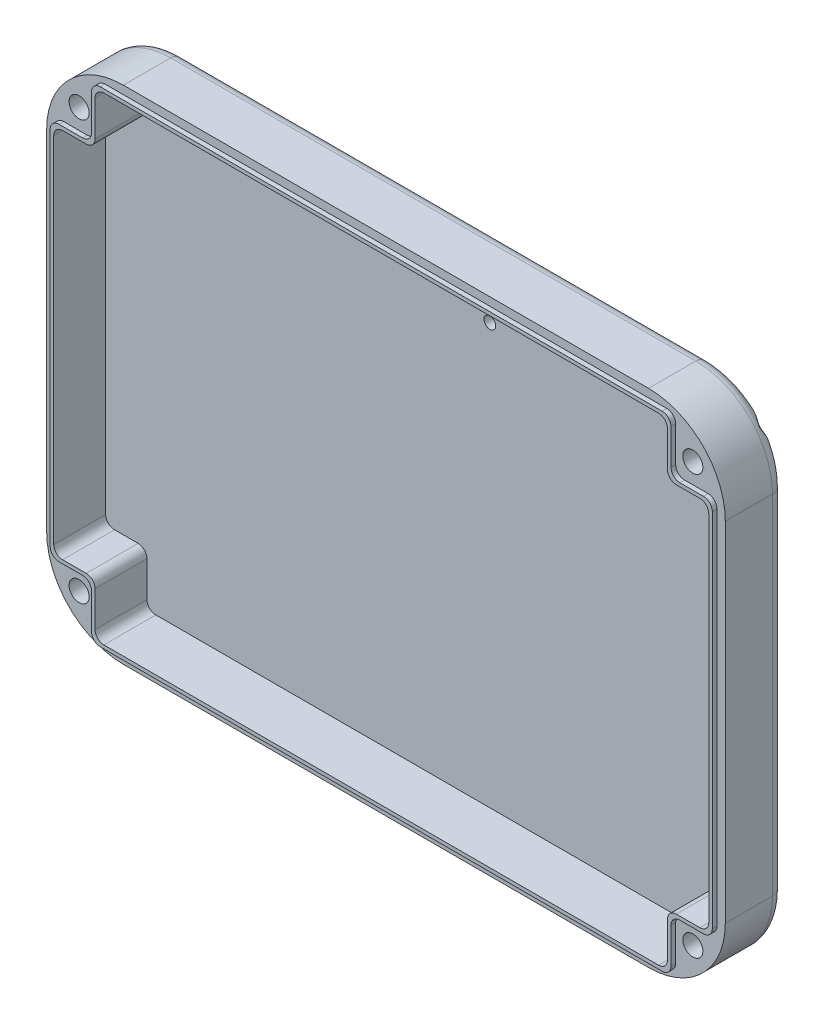
SolidWorks part; units mm, degrees
ref_plane "Спереди" through (0, 0, 0) normal (0, 0, 1) x (1, 0, 0)
ref_plane "Сверху" through (0, 0, 0) normal (0, 1, 0) x (1, 0, 0)
ref_plane "Справа" through (0, 0, 0) normal (1, 0, 0) x (0, 0, -1)
sketch "Sketch1" plane through (0, 0, 0) normal (0, 0, 1) x (1, 0, 0)
  line L1 (-57.5, 85) -> (57.5, 85) construction
  line L2 (-57.5, 85) -> (-57.5, 0) construction
  line L3 (-57.5, 0) -> (57.5, 0) construction
  line L5 (-57.5, 42.5) -> (22.5, 42.5) construction
  line L7 (0, 0) -> (0, 85) construction
  line L10 (-57.5, 85) -> (-57.5, 0) construction
  line L11 (-57.5, 85) -> (57.5, 85)
  line L12 (57.5, 85) -> (57.5, 0) construction
  line L13 (57.5, 0) -> (-57.5, 0)
  line L20 (57.5, 0) -> (57.5, 19)
  line L21 (57.5, 19) -> (57.5, 85)
  line L22 (-57.5, 0) -> (-57.5, 19)
  line L23 (-57.5, 19) -> (-57.5, 85)
  dimension "D1" = 115
  dimension "D2" = 85
extrude "Boss-Extrude1" add sketch "Sketch1" along normal blind 10
shell "Shell1" thickness 2 removed face at (0, 42.5, 10)
sketch "Sketch3" plane through (0, 0, 2) normal (0, 0, 1) x (1, 0, 0)
  line L0 (0, 0) -> (0, 85) construction
  line L1 (55.5, 2) -> (48.5, 2)
  line L2 (55.5, 2) -> (55.5, 11)
  line L3 (55.5, 11) -> (48.5, 11)
  line L4 (48.5, 2) -> (48.5, 11)
  line L5 (-57.5, 0) -> (57.5, 0) construction
  line L6 (57.5, 85) -> (-57.5, 85) construction
  line L7 (-48.5, 2) -> (-48.5, 11)
  line L8 (55.5, 2) -> (55.5, 83) construction
  line L9 (55.5, 42.5) -> (-55.5, 42.5) construction
  line L10 (-55.5, 83) -> (-55.5, 2) construction
  line L11 (-55.5, 11) -> (-48.5, 11)
  line L12 (-55.5, 2) -> (-55.5, 11)
  line L13 (-55.5, 2) -> (-48.5, 2)
  line L14 (-55.5, 83) -> (-48.5, 83)
  line L15 (-55.5, 83) -> (-55.5, 74)
  line L16 (-55.5, 74) -> (-48.5, 74)
  line L17 (-48.5, 83) -> (-48.5, 74)
  line L18 (48.5, 83) -> (48.5, 74)
  line L19 (55.5, 74) -> (48.5, 74)
  line L20 (55.5, 83) -> (55.5, 74)
  line L21 (55.5, 83) -> (48.5, 83)
  line L22 (57.5, 0) -> (57.5, 85) construction
  circle A0 centre (52, 7) radius 1.7
  circle A1 centre (-52, 7) radius 1.7
  circle A2 centre (-52, 78) radius 1.7
  circle A3 centre (52, 78) radius 1.7
  dimension "D3" = 3.4
  dimension "D1" = 7
  dimension "D2" = 9
  dimension "D4" = 7
  dimension "D5" = 5.5
extrude "Boss-Extrude3" add sketch "Sketch3" along normal up to surface (8 mm away) up to face at (0, 42.5, 10)
sketch "Sketch5" plane through (0, 0, 10) normal (0, 0, 1) x (1, 0, 0)
  line L0 (0, 0) -> (0, 85) construction
  line L1 (-57.5, 0) -> (57.5, 0) construction
  line L2 (57.5, 85) -> (-57.5, 85) construction
  line L4 (55.5, 11) -> (55.5, 74) construction
  line L5 (55.5, 42.5) -> (-55.5, 42.5) construction
  line L6 (55.5, 11) -> (55.5, 74) construction
  line L7 (56.1, 10.4) -> (56.1, 54.9886) construction
  line L8 (55.5, 11) -> (48.5, 11)
  line L9 (48.5, 11) -> (48.5, 2)
  line L10 (48.5, 2) -> (0, 2)
  line L11 (-48.5, 2) -> (48.5, 2) construction
  line L42 (55.5, 11) -> (55.5, 42.5)
  line L49 (56.1, 10.4) -> (49.1, 10.4)
  line L50 (49.1, 10.4) -> (49.1, 1.4)
  line L51 (49.1, 1.4) -> (0, 1.4)
  line L52 (-49.1, 1.4) -> (0, 1.4)
  line L53 (-49.1, 10.4) -> (-49.1, 1.4)
  line L54 (-56.1, 10.4) -> (-49.1, 10.4)
  line L58 (-55.5, 11) -> (-55.5, 42.5)
  line L61 (-48.5, 2) -> (0, 2)
  line L62 (-48.5, 11) -> (-48.5, 2)
  line L63 (-55.5, 11) -> (-48.5, 11)
  line L64 (-55.5, 74) -> (-48.5, 74)
  line L65 (-48.5, 74) -> (-48.5, 83)
  line L66 (-48.5, 83) -> (0, 83)
  line L68 (-55.5, 74) -> (-55.5, 42.5)
  line L70 (-56.1, 74.6) -> (-56.1, 10.4)
  line L71 (-56.1, 74.6) -> (-49.1, 74.6)
  line L72 (-49.1, 74.6) -> (-49.1, 83.6)
  line L73 (-49.1, 83.6) -> (0, 83.6)
  line L74 (49.1, 83.6) -> (0, 83.6)
  line L75 (49.1, 74.6) -> (49.1, 83.6)
  line L76 (56.1, 74.6) -> (49.1, 74.6)
  line L77 (56.1, 74.6) -> (56.1, 10.4)
  line L80 (55.5, 74) -> (55.5, 42.5)
  line L83 (48.5, 83) -> (0, 83)
  line L84 (48.5, 74) -> (48.5, 83)
  line L85 (55.5, 74) -> (48.5, 74)
  line L86 (42.6, -85.1835) -> (42.6, 29) construction
  line L87 (56.1, 54.9886) -> (42.6, -85.1835) construction
  line L88 (55.5, 42.5) -> (42, -97.6721) construction
  line L89 (42, -97.6721) -> (42, 29) construction
  line L90 (57.5, 85) -> (-57.5, 85) construction
  dimension "D1" = 42.5
  dimension "D2" = 0.6
extrude "Boss-Extrude4" add sketch "Sketch5" along normal blind 0.8
fillet "Fillet6" radius 1.5 12 edges at (-48.5, 2, 6.4) (-48.5, 11, 6.4) (-55.5, 11, 6.4) (-55.5, 74, 6.4) (-48.5, 74, 6.4) (-48.5, 83, 6.4) (48.5, 83, 6.4) (48.5, 74, 6.4) (55.5, 74, 6.4) (48.5, 2, 6.4) (55.5, 11, 6.4) (48.5, 11, 6.4)
fillet "Fillet7" radius 1.5 12 edges at (49.1, 10.4, 10.4) (49.1, 1.4, 10.4) (-49.1, 1.4, 10.4) (-49.1, 10.4, 10.4) (-56.1, 74.6, 10.4) (-49.1, 74.6, 10.4) (-49.1, 83.6, 10.4) (49.1, 83.6, 10.4) (49.1, 74.6, 10.4) (56.1, 74.6, 10.4) (-56.1, 10.4, 10.4) (56.1, 10.4, 10.4)
fillet "Fillet8" radius 13 4 edges at (-57.5, 0, 5) (-57.5, 85, 5) (57.5, 85, 5) (57.5, 0, 5)
fillet "Fillet11" radius 2 8 edges at (53.6924, 81.1924, 0) (57.5, 42.5, 0) (53.6924, 3.8076, 0) (0, 0, 0) (-53.6924, 3.8076, 0) (-57.5, 42.5, 0) (-53.6924, 81.1924, 0) (0, 85, 0)
ref_plane "Plane1" through (0, 42.5, 0) normal (0, -1, 0) x (-1, 0, 0)
ref_plane "Plane2" through (0, 0, 0) normal (1, 0, 0) x (0, 0, -1)
ref_plane "Plane3" through (0, 0, 7.5) normal (0, 0, 1) x (1, 0, 0)
sketch "Sketch17" plane through (0, 0, 0) normal (0, 0, -1) x (-1, 0, 0)
  line L0 (0, 0) -> (0, 85) construction
  line L2 (-44.5, 85) -> (44.5, 85) construction
  line L3 (0, 85) -> (55.5, 42.5) construction
  line L4 (55.5, 42.5) -> (-55.5, 42.5) construction
  line L5 (44.5, 0) -> (-44.5, 0) construction
  circle A0 centre (52, 7) radius 1.7
  circle A1 centre (-52, 7) radius 1.7
  circle A2 centre (-52, 78) radius 1.7
  circle A3 centre (52, 78) radius 1.7
  dimension "D1" = 3.4
extrude "Cut-Extrude5" cut sketch "Sketch17" against normal blind 10
sketch "Sketch18" plane through (0, 0, 0) normal (0, 0, -1) x (-1, 0, 0)
  line L0 (0, 0) -> (0, 85) construction
  line L1 (-57.5, 13) -> (-57.5, 72) construction
  line L2 (-44.5, 85) -> (44.5, 85) construction
  line L4 (57.5, 72) -> (57.5, 13) construction
  line L5 (57.5, 42.5) -> (-57.5, 42.5) construction
  circle A0 centre (52, 7) radius 2.5
  circle A1 centre (-52, 7) radius 2.5
  circle A2 centre (-52, 78) radius 2.5
  circle A3 centre (52, 78) radius 2.5
  dimension "D1" = 5
extrude "Cut-Extrude6" cut sketch "Sketch18" against normal blind 5
fillet "Fillet16" radius 0.4 8 edges at (-54.3011, 78.9773, 0.2862) (-53.4586, 4.9696, 0.2862) (-50.0478, 8.5617, 0) (54.3011, 6.0227, 0.2862) (50.0478, 76.4383, 0) (-50.0478, 76.4383, 0) (50.0478, 8.5617, 0) (53.4586, 80.0304, 0.2862)
ref_plane "Plane4" through (0, 19, 0) normal (0, -1, 0) x (-1, 0, 0)
ref_plane "Plane5" through (0, 0, 0) normal (1, 0, 0) x (0, 0, -1)
sketch "Sketch19" plane through (0, 0, 0) normal (0, 0, -1) x (-1, 0, 0)
  circle A0 centre (-9.6, 73.2) radius 1
  point P2 (0, 0)
  dimension "D1" = 2
  dimension "D2" = 1.155
extrude "Cut-Extrude7" cut sketch "Sketch19" against normal blind 10
